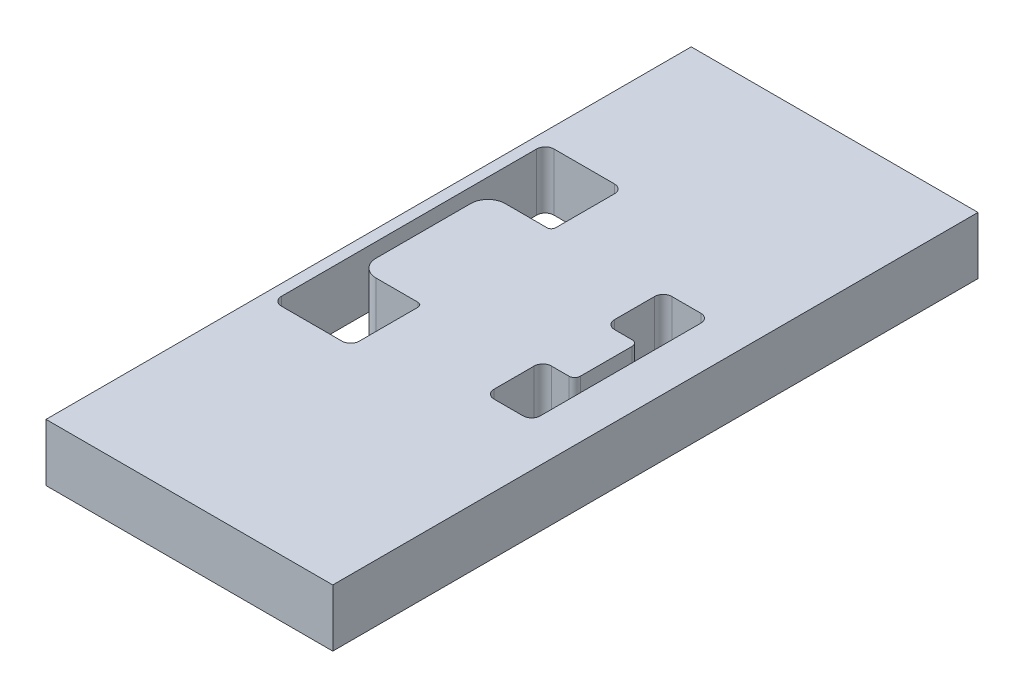
SolidWorks part; units mm, degrees
material "Plain Carbon Steel"
ref_plane "Front Plane" through (0, 0, 0) normal (0, 0, 1) x (1, 0, 0)
ref_plane "Top Plane" through (0, 0, 0) normal (0, 1, 0) x (1, 0, 0)
ref_plane "Right Plane" through (0, 0, 0) normal (1, 0, 0) x (0, 0, -1)
sketch "Sketch1" plane through (0, 0, 0) normal (0, 1, 0) x (1, 0, 0)
  line L1 (-50, -112.5) -> (50, -112.5)
  line L2 (-50, -112.5) -> (-50, 112.5)
  line L3 (-50, 112.5) -> (50, 112.5)
  line L4 (50, -112.5) -> (50, 112.5)
  line L5 (-50, -112.5) -> (50, 112.5) construction
  line L6 (-50, 112.5) -> (50, -112.5) construction
  point P0 (0, 0)
  dimension "D1" = 225
  dimension "D2" = 100
extrude "Boss-Extrude1" add sketch "Sketch1" along normal blind 20
sketch "Sketch2" plane through (0, 20, 0) normal (0, 1, 0) x (1, 0, 0)
  line L0 (-43.12, 37.73) -> (-19, 37.73) construction
  line L1 (-43.12, -17.27) -> (-19, -17.27) construction
  line L8 (-41.12, 26.73) -> (-41.12, -6.27) construction
  line L9 (-43.12, -37.27) -> (-22, -37.27)
  line L11 (-43.12, 57.73) -> (-22, 57.73)
  line L13 (-20.5, 32.73) -> (-35.12, 32.73) construction
  line L14 (-19, 37.73) -> (-19, 34.23) construction
  line L16 (-46.12, 34.73) -> (-46.12, -14.27) construction
  line L18 (-19, -17.27) -> (-19, -13.77) construction
  line L19 (-35.12, -12.27) -> (-20.5, -12.27) construction
  line L20 (-41.12, 26.73) -> (-41.12, -6.27)
  line L21 (-20.5, 32.73) -> (-35.12, 32.73)
  line L22 (-19, 54.73) -> (-19, 34.23)
  line L24 (-46.12, 54.73) -> (-46.12, -34.27)
  line L26 (-19, -34.27) -> (-19, -13.77)
  line L27 (-35.12, -12.27) -> (-20.5, -12.27)
  arc A0 (-22, 57.73) -> (-19, 54.73) centre (-22, 54.73) cw
  arc A1 (-46.12, 54.73) -> (-43.12, 57.73) centre (-43.12, 54.73) cw
  arc A2 (-43.12, -37.27) -> (-46.12, -34.27) centre (-43.12, -34.27) cw
  arc A3 (-22, -37.27) -> (-19, -34.27) centre (-22, -34.27) ccw
  arc A6 (-41.12, -6.27) -> (-35.12, -12.27) centre (-35.12, -6.27) ccw construction
  arc A7 (-35.12, 32.73) -> (-41.12, 26.73) centre (-35.12, 26.73) ccw construction
  arc A8 (-20.5, 32.73) -> (-19, 34.23) centre (-20.5, 34.23) ccw construction
  arc A11 (-19, -13.77) -> (-20.5, -12.27) centre (-20.5, -13.77) ccw construction
  arc A12 (-41.12, -6.27) -> (-35.12, -12.27) centre (-35.12, -6.27) ccw
  arc A13 (-35.12, 32.73) -> (-41.12, 26.73) centre (-35.12, 26.73) ccw
  arc A14 (-20.5, 32.73) -> (-19, 34.23) centre (-20.5, 34.23) ccw
  arc A17 (-19, -13.77) -> (-20.5, -12.27) centre (-20.5, -13.77) ccw
  dimension "D3" = 3
  dimension "D1" = 20
  dimension "D2" = 20
extrude "Cut-Extrude1" cut sketch "Sketch2" against normal up to next
sketch "Sketch3" plane through (0, 20, 0) normal (0, 1, 0) x (1, 0, 0)
  line L0 (22, -8.27) -> (28.13, -8.27) construction
  line L1 (19, -13.27) -> (19, -11.27) construction
  line L3 (35.13, 15.73) -> (35.13, -10.27) construction
  line L5 (19, 18.73) -> (19, 16.73) construction
  line L6 (28.13, 13.73) -> (22, 13.73) construction
  line L7 (30.13, -6.27) -> (30.13, 11.73) construction
  line L8 (22, -8.27) -> (28.13, -8.27)
  line L9 (19, -25.27) -> (19, -11.27)
  line L11 (35.13, 30.73) -> (35.13, -25.27)
  line L13 (19, 30.73) -> (19, 16.73)
  line L14 (28.13, 13.73) -> (22, 13.73)
  line L15 (30.13, -6.27) -> (30.13, 11.73)
  line L16 (22, -28.27) -> (32.13, -28.27)
  line L17 (22, 33.73) -> (32.13, 33.73)
  line L18 (19, 18.73) -> (32.13, 18.73) construction
  line L19 (32.13, -13.27) -> (19, -13.27) construction
  arc A0 (28.13, -8.27) -> (30.13, -6.27) centre (28.13, -6.27) ccw construction
  arc A1 (22, -8.27) -> (19, -11.27) centre (22, -11.27) ccw construction
  arc A4 (19, 16.73) -> (22, 13.73) centre (22, 16.73) ccw construction
  arc A5 (30.13, 11.73) -> (28.13, 13.73) centre (28.13, 11.73) ccw construction
  arc A6 (28.13, -8.27) -> (30.13, -6.27) centre (28.13, -6.27) ccw
  arc A7 (22, -8.27) -> (19, -11.27) centre (22, -11.27) ccw
  arc A10 (19, 16.73) -> (22, 13.73) centre (22, 16.73) ccw
  arc A11 (30.13, 11.73) -> (28.13, 13.73) centre (28.13, 11.73) ccw
  arc A12 (22, 33.73) -> (19, 30.73) centre (22, 30.73) ccw
  arc A13 (32.13, 33.73) -> (35.13, 30.73) centre (32.13, 30.73) cw
  arc A14 (32.13, -28.27) -> (35.13, -25.27) centre (32.13, -25.27) ccw
  arc A15 (22, -28.27) -> (19, -25.27) centre (22, -25.27) cw
  dimension "D3" = 3
  dimension "D1" = 15
  dimension "D2" = 15
extrude "Cut-Extrude2" cut sketch "Sketch3" against normal up to next
